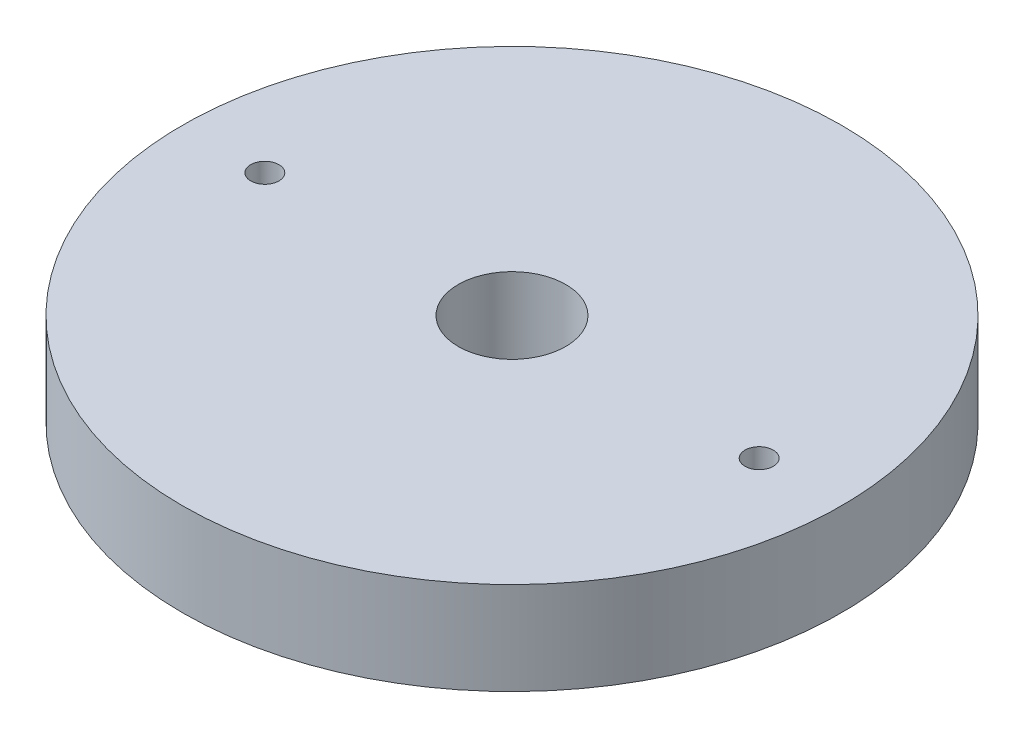
SolidWorks part; units mm, degrees
ref_plane "Front Plane" through (0, 0, 0) normal (0, 0, 1) x (1, 0, 0)
ref_plane "Top Plane" through (0, 0, 0) normal (0, 1, 0) x (1, 0, 0)
ref_plane "Right Plane" through (0, 0, 0) normal (1, 0, 0) x (0, 0, -1)
sketch "Sketch1" plane through (0, 0, 0) normal (0, 1, 0) x (1, 0, 0)
  line L0 (0, 0) -> (-13.335, 0) construction
  line L1 (0, 0) -> (13.335, 0) construction
  circle A0 centre (0, 0) radius 17.78
  circle A1 centre (-13.335, 0) radius 0.762
  circle A2 centre (13.335, 0) radius 0.762
  point P6 (0, 0)
  dimension "D1" = 35.56
  dimension "D2" = 1.524
  dimension "D3" = 1.524
  dimension "D4" = 26.67
extrude "Boss-Extrude1" add sketch "Sketch1" along normal blind 5
sketch "Sketch5" plane through (0, 0, 0) normal (0, -1, 0) x (1, 0, 0)
  circle A0 centre (0, 13.97) radius 2.667
  dimension "D1" = 5.334
  dimension "D2" = 13.97
extrude "Cut-Extrude1" cut sketch "Sketch5" against normal blind 3
hole_wizard "M5 Clearance Hole2" positions "Sketch8" profile "Sketch9" hole size "M5" standard "ANSI Metric" end condition through all
sketch "Sketch8" plane through (0, 5, 0) normal (0, 1, 0) x (1, 0, 0)
  point P0 (0, 0)
sketch "Sketch9" plane through (0, 5, 0) normal (1, 0, 0) x (0, 0, 1)
  line L0 (0, 0) -> (0, 5)
  line L1 (0, 5) -> (2.9, 5)
  line L2 (2.9, 5) -> (2.9, 0)
  line L5 (2.9, 0) -> (0, 0)
  line L11 (0, -6.35) -> (0, 107.95) construction
  dimension "Thru Hole Dia." = 5.8
  dimension "Thru Hole Depth" = 5
equation "\"press fit\"= 0.25mm"
equation "\"servo hole size\"= 0.0472in + \"press fit\""
equation "\"D2@Sketch1\"=\"servo hole size\""
equation "\"D3@Sketch1\"=\"servo hole size\""
equation "\"hole distance\"= 1.05in"
equation "\"D4@Sketch1\"=\"hole distance\""
equation "\"pin diamiter\"= 5mm"
equation "\"D1@Sketch5\"=\"pin diamiter\"+\"press fit\""
equation "\"middle hole\"= 0.2in"
